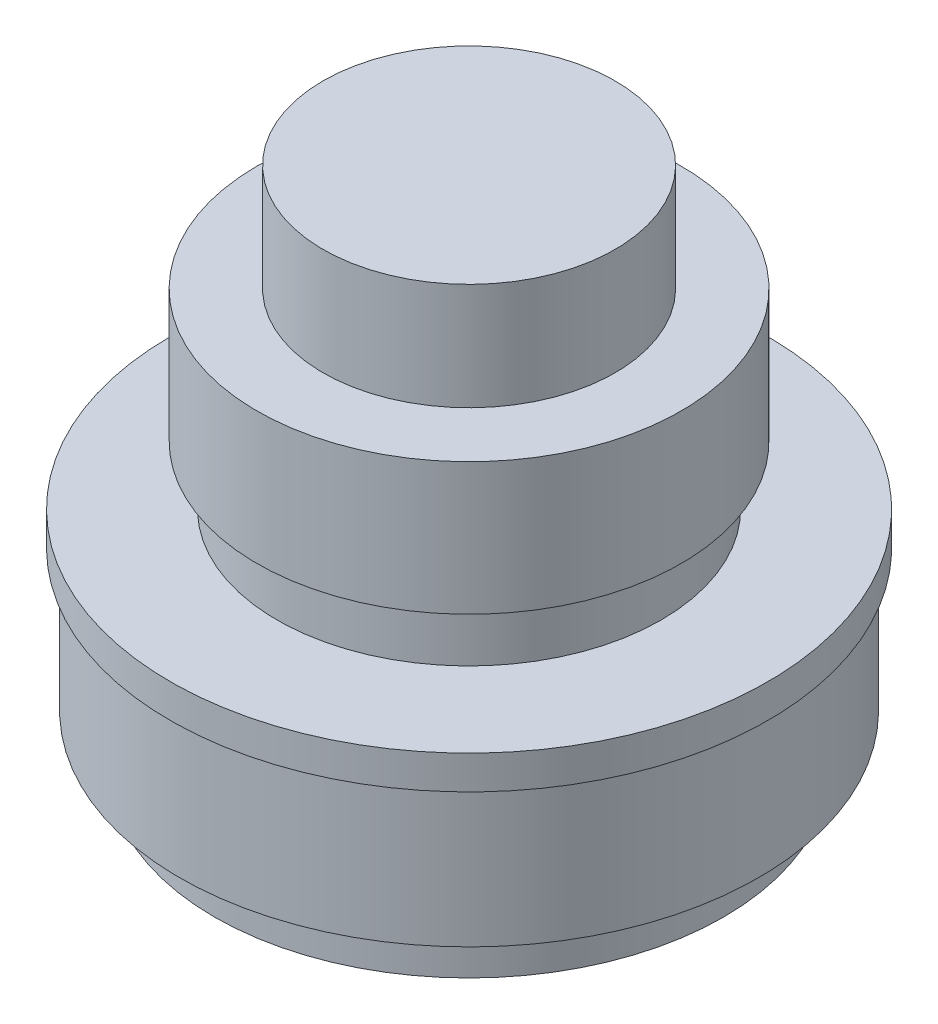
SolidWorks part; units mm, degrees
ref_plane "Front Plane" through (0, 0, 0) normal (0, 0, 1) x (1, 0, 0)
ref_plane "Top Plane" through (0, 0, 0) normal (0, 1, 0) x (1, 0, 0)
ref_plane "Right Plane" through (0, 0, 0) normal (1, 0, 0) x (0, 0, -1)
sketch "Sketch3" plane through (0, 0, 0) normal (0, 0, 1) x (1, 0, 0)
  line L0 (0, 5.6622) -> (0, -39.9378)
  line L1 (0, 5.6622) -> (-12.71, 5.6622)
  line L2 (-12.71, 5.6622) -> (-12.71, -3.6378)
  line L3 (-12.71, -3.6378) -> (-18.46, -3.6378)
  line L4 (-18.46, -3.6378) -> (-18.46, -15.1378)
  line L5 (-18.46, -15.1378) -> (-16.715, -15.1378)
  line L6 (-16.715, -15.1378) -> (-16.715, -20.2678)
  line L7 (-16.715, -20.2678) -> (-26.005, -20.2678)
  line L8 (-26.005, -20.2678) -> (-26.005, -23.1935)
  line L9 (-26.005, -23.1935) -> (-25.2, -23.1935)
  line L10 (-25.2, -23.1935) -> (-25.2, -35.4435)
  line L11 (-25.2, -35.4435) -> (-22.155, -35.4435)
  line L12 (-22.155, -35.4435) -> (-22.155, -39.9378)
  line L13 (-22.155, -39.9378) -> (0, -39.9378)
  point P3 (-19.5843, -35.4435)
  point P16 (0, 0)
  point P17 (-22.155, -39.9378)
  dimension "D1" = 45.6
  dimension "D2" = 12.71
  dimension "D3" = 9.3
  dimension "D4" = 5.75
  dimension "D5" = 11.5
  dimension "D6" = 1.745
  dimension "D7" = 5.13
  dimension "D8" = 9.29
  dimension "D9" = 12.25
  dimension "D10" = 3.045
  dimension "D11" = 0.805
revolve "Revolve1" add sketch "Sketch3" angle 360 about L0
